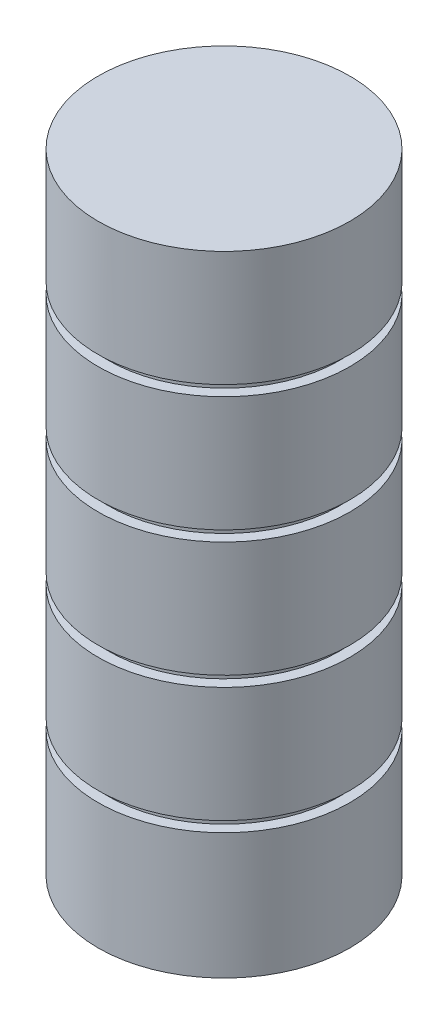
SolidWorks part; units mm, degrees
ref_plane "Front Plane" through (0, 0, 0) normal (0, 0, 1) x (1, 0, 0)
ref_plane "Top Plane" through (0, 0, 0) normal (0, 1, 0) x (1, 0, 0)
ref_plane "Right Plane" through (0, 0, 0) normal (1, 0, 0) x (0, 0, -1)
sketch "Sketch1" plane through (0, 0, 0) normal (0, 1, 0) x (1, 0, 0)
  circle A0 centre (0, 0) radius 6
  dimension "D1" = 12
extrude "Boss-Extrude1" add sketch "Sketch1" along normal blind 30
sketch "Sketch2" plane through (0, 0, 0) normal (0, 0, 1) x (1, 0, 0)
  line L0 (6, 0) -> (6, 30) construction
  line L1 (5.5, 6.5) -> (6, 6.5)
  line L2 (5.5, 6.5) -> (5.5, 6)
  line L3 (5.5, 6) -> (6, 6)
  line L4 (6, 6.5) -> (6, 6)
  line L5 (-6, 0) -> (6, 0) construction
  line L6 (6, 12.5) -> (6, 12)
  line L7 (5.5, 12) -> (6, 12)
  line L8 (5.5, 12.5) -> (5.5, 12)
  line L9 (5.5, 12.5) -> (6, 12.5)
  line L10 (6, 18.5) -> (6, 18)
  line L11 (5.5, 18) -> (6, 18)
  line L12 (5.5, 18.5) -> (5.5, 18)
  line L13 (5.5, 18.5) -> (6, 18.5)
  line L14 (6, 24.5) -> (6, 24)
  line L15 (5.5, 24) -> (6, 24)
  line L16 (5.5, 24.5) -> (5.5, 24)
  line L17 (5.5, 24.5) -> (6, 24.5)
  line L18 (0, 0) -> (0, 30) construction
  line L19 (6, 30) -> (-6, 30) construction
  dimension "D1" = 0.5
  dimension "D2" = 6
  dimension "D4" = 5.5
  dimension "D3" = 4
revolve "Cut-Revolve1" cut sketch "Sketch2" angle 360 about L18
hole_wizard "M6 Tapped Hole1" positions "Sketch3" profile "Sketch4" tap size "M6" standard "ISO"
sketch "Sketch3" plane through (0, 0, 0) normal (0, -1, 0) x (-1, 0, 0)
  point P0 (0, 0)
sketch "Sketch4" plane through (0, 0, 0) normal (1, 0, 0) x (0, 0, -1)
  line L0 (0, 0) -> (0, 13.5022)
  line L1 (0, 13.5022) -> (2.5, 12)
  line L2 (2.5, 12) -> (2.5, 0)
  line L5 (2.5, 0) -> (0, 0)
  line L10 (0, 13.5022) -> (-2.5, 12) construction
  line L11 (0, -6.35) -> (0, 107.95) construction
  dimension "Tap Drill Dia." = 5
  dimension "Tap Drill Depth" = 12
  dimension "Drill Angle" = 118
cosmetic thread "Hole Thread1" parameters "D1"=10, "D2"=6
thread "Thread1" pitch 1 method cut profile "Thread Profile1" start angle 0, offset 0, length 0, pitch 1, diameter 5
ref_plane "Plane1" through (-2.5, 12, 0) normal (0, 0, 1) x (-1, 0, 0)
sketch "Thread Profile1" plane through (-2.5, 12, 0) normal (0, 0, 1) x (-1, 0, 0)
  line L0 (0, 0) -> (0, 1) construction
  line L1 (0, 0) -> (0.5413, 0.3125)
  line L2 (0.5413, 0.3125) -> (0.5413, 0.4375)
  line L3 (0.5413, 0.4375) -> (0, 0.75)
  line L4 (0.5413, 0.375) -> (0, 0.375) construction
  line L11 (0, 0) -> (0, 0.75)
  point P2 (0, 0)
  dimension "Pitch" = 1
  dimension "Profile_Angle" = 60
  dimension "Profile_Land" = 0.125
  dimension "Profile_Height" = 0.5413
